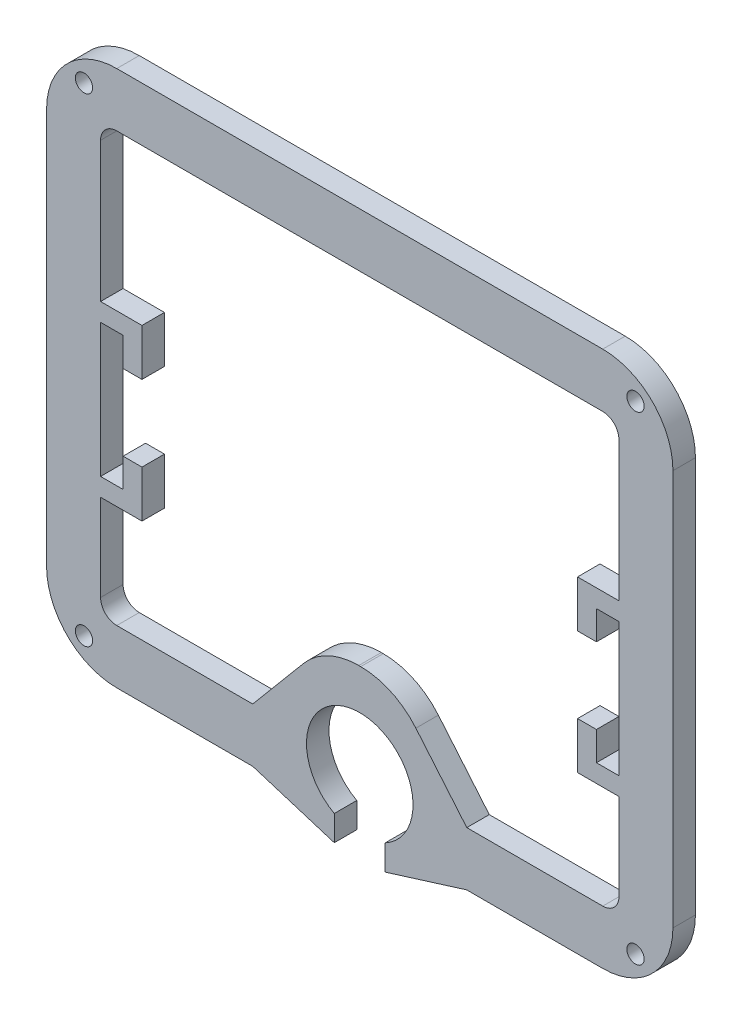
SolidWorks part; units mm, degrees
material "Delrin 2700 NC010, Low Viscosity Acetal Copolymer (SS)"
ref_plane "Front Plane" through (0, 0, 0) normal (0, 0, 1) x (1, 0, 0)
ref_plane "Top Plane" through (0, 0, 0) normal (0, 1, 0) x (1, 0, 0)
ref_plane "Right Plane" through (0, 0, 0) normal (1, 0, 0) x (0, 0, -1)
sketch "Sketch1" plane through (0, 0, 0) normal (0, 0, 1) x (1, 0, 0)
  line L0 (-17.145, -18.923) -> (-7.5425, -18.923)
  line L1 (-18.288, 13.97) -> (-18.288, -13.97)
  line L2 (-17.145, -15.113) -> (-7.5521, -15.113)
  line L3 (7.5521, -15.113) -> (17.145, -15.113)
  line L4 (18.288, 13.97) -> (18.288, -13.97)
  line L5 (-1000, 0) -> (49000, 0) construction
  line L6 (-1.7968, -18.923) -> (-1.7968, -20.7107)
  line L7 (7.5425, -18.923) -> (17.145, -18.923)
  line L8 (17.145, 15.113) -> (-17.145, 15.113)
  line L9 (-7.5521, -15.113) -> (-3.9596, -10.8316)
  line L10 (-22.098, 13.97) -> (-22.098, -13.97)
  line L11 (7.5521, -15.113) -> (3.9596, -10.8316)
  line L12 (-0.0681, -9.017) -> (0.0681, -9.017)
  line L13 (22.098, 13.97) -> (22.098, -13.97)
  line L14 (17.145, 18.923) -> (-17.145, 18.923)
  line L15 (1.7968, -18.923) -> (1.7968, -20.7107)
  line L16 (-7.5425, -18.923) -> (-1.7968, -20.7107)
  line L17 (7.5425, -18.923) -> (1.7968, -20.7107)
  line L18 (0, 12.5532) -> (0, -24.2768) construction
  line L19 (1.7968, -18.923) -> (17.145, -18.923) construction
  line L20 (-17.145, -18.923) -> (-1.7968, -18.923) construction
  arc A0 (1.7968, -18.923) -> (-1.7968, -18.923) centre (0, -15.621) ccw
  arc A1 (-17.145, -15.113) -> (-18.288, -13.97) centre (-17.145, -13.97) cw
  arc A2 (-0.0681, -9.017) -> (-3.9596, -10.8316) centre (-0.0681, -14.097) ccw
  arc A3 (18.288, -13.97) -> (17.145, -15.113) centre (17.145, -13.97) cw
  arc A4 (17.145, 15.113) -> (18.288, 13.97) centre (17.145, 13.97) cw
  arc A5 (-17.145, -18.923) -> (-22.098, -13.97) centre (-17.145, -13.97) cw
  arc A6 (22.098, -13.97) -> (17.145, -18.923) centre (17.145, -13.97) cw
  arc A7 (17.145, 18.923) -> (22.098, 13.97) centre (17.145, 13.97) cw
  arc A8 (-17.145, 18.923) -> (-22.098, 13.97) centre (-17.145, 13.97) ccw
  circle A9 centre (-19.4575, 16.891) radius 0.6096
  circle A10 centre (19.4575, 16.891) radius 0.6096
  arc A11 (-17.145, 15.113) -> (-18.288, 13.97) centre (-17.145, 13.97) ccw
  arc A12 (0.0681, -9.017) -> (3.9596, -10.8316) centre (0.0681, -14.097) cw
  circle A13 centre (19.4575, -16.891) radius 0.6096
  circle A14 centre (-19.4575, -16.891) radius 0.6096
  circle A15 centre (0, -15.621) radius 5.3975 construction
  arc A18 (7.5521, -15.113) -> (-7.5521, -15.113) centre (0, -15.621) ccw construction
  point P0 (0, 0)
  dimension "D4" = 3.302
  dimension "D6" = 37.846
  dimension "D7" = 44.196
  dimension "D8" = 3.81
  dimension "D9" = 6.604
  dimension "D5" = 1.2192
  dimension "D2" = 4.953
  dimension "D3" = 7.5184
  dimension "D10" = 5.08
  dimension "D11" = 5.08
  dimension "D14" = 10.795
  dimension "D12" = 16.891
  dimension "D13" = 19.4575
extrude "Boss-Extrude1" add sketch "Sketch1" along normal blind 1.5875
sketch "Sketch2" plane through (-18.288, 0, 0) normal (1, 0, 0) x (0, 0, -1)
  line L0 (0, 2.8448) -> (-1.5875, 2.8448)
  line L1 (0, -6.574) -> (-1.5875, -6.574) construction
  line L2 (-1.5875, -15.113) -> (0, -15.113)
  line L3 (-1.5875, -15.113) -> (0, -15.113) construction
  line L4 (0, -13.97) -> (0, 13.97)
  line L5 (0, 13.97) -> (-1.5875, 13.97)
  line L6 (-1.5875, 13.97) -> (-1.5875, -13.97)
  line L7 (0, 13.97) -> (-1.5875, 13.97)
  line L8 (0, -13.97) -> (0, 4.1148)
  line L9 (-1.5875, -15.113) -> (-1.5875, -7.844)
  line L10 (-1.5875, 4.1148) -> (-1.5875, -13.97)
  line L11 (-1.5875, -13.97) -> (0, -13.97)
  line L12 (0, -15.113) -> (0, -7.844)
  line L13 (0, 4.1148) -> (-1.5875, 4.1148)
  line L14 (-1.5875, 2.8448) -> (-1.5875, -6.6447)
  line L15 (-1.5875, 4.1148) -> (-1.5875, 2.8448)
  line L16 (0, 2.8448) -> (0, 4.1148)
  line L17 (0, -7.9147) -> (0, 1.4693)
  line L18 (-1.5875, -7.9147) -> (-1.5875, -6.6447)
  line L19 (0, -6.574) -> (-1.5875, -6.574)
  line L21 (0, -7.844) -> (-1.5875, -7.844)
  line L22 (0, -7.844) -> (0, -13.97)
  line L23 (-1.5875, -7.844) -> (-1.5875, -13.97)
  line L24 (47.9467, 2.8448) -> (-13.6743, 2.8448) construction
  line L28 (-1.5875, -13.97) -> (0, -13.97)
  line L29 (47.5364, -9.6894) -> (-13.6984, -5.6762) construction
  line M5 (0, -13.97) -> (0, 13.97)
  line M7 (-1.5875, 13.97) -> (-1.5875, -13.97)
  dimension "D1" = 0
  dimension "D2" = 1.27
  dimension "D4" = 1.27
extrude "Boss-Extrude2" add sketch "Sketch2" along normal blind 2.921 contours L13 L10 L0 M5 | L19 L17 L8 L0 L10 M7 | L21 L8 L19 L18 M5 M7 region at (-18.288, -1.8646, 0.7937) region at (-18.288, 3.4798, 0.7937) region at (-18.288, -7.209, 0.7937)
extrude "Cut-Extrude1" cut sketch "Sketch2<3>" along normal blind 1.5875 contours L19 L8 L10 | L19 L17 L0 M5 M7 region at (-18.288, -1.8646, 0.7937)
sketch "Sketch2<3>" plane through (-18.288, 0, 0) normal (1, 0, 0) x (0, 0, -1) same geometry as "Sketch2"
sketch "Sketch3" plane through (-16.7005, 0, 0) normal (-1, 0, 0) x (0, 0, 1)
  line L0 (0, 2.8448) -> (1.5875, 2.8448) construction
  line L1 (0, -6.574) -> (1.5875, -6.574) construction
  line L2 (0, 2.8448) -> (1.5875, 2.8448)
  line L3 (0, -6.574) -> (1.5875, -6.574)
  line L4 (0, 0.8128) -> (1.5875, 0.8128)
  line L5 (0, -4.542) -> (1.5875, -4.542)
  line L6 (1.5875, 0.8128) -> (1.5875, -4.542)
  line L7 (0, -4.542) -> (0, 0.8128)
  line M2 (1.5875, -6.574) -> (1.5875, 2.8448)
  line M4 (0, 2.8448) -> (0, -6.574)
  dimension "D1" = 2.032
  dimension "D2" = 2.032
extrude "Cut-Extrude2" cut sketch "Sketch3" against normal up to surface (1.3335 mm away) contours L5 L4 M4 M2 region at (-16.7005, -1.8646, 0.7937) up to face at (-15.367, -1.8646, 0.7937)
mirror "Mirror1" about plane through (0, 0, 0) normal (1, 0, 0) of "Cut-Extrude2", "Boss-Extrude2", "Cut-Extrude1"
